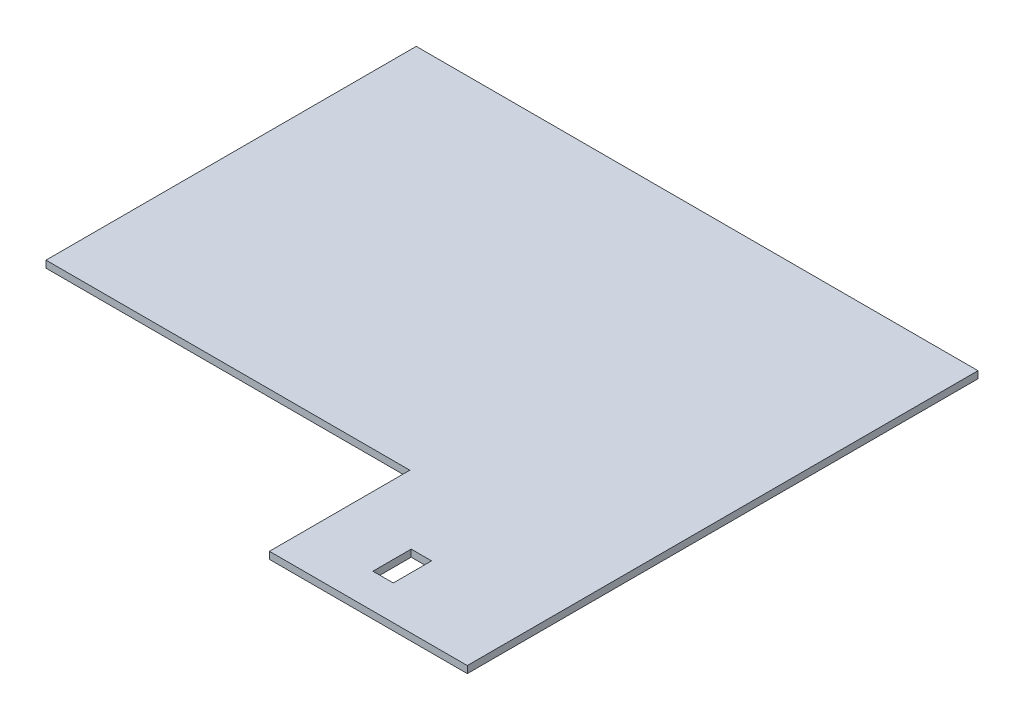
SolidWorks part; units mm, degrees
ref_plane "Alzado" through (0, 0, 0) normal (0, 0, 1) x (1, 0, 0)
ref_plane "Planta" through (0, 0, 0) normal (0, 1, 0) x (1, 0, 0)
ref_plane "Vista lateral" through (0, 0, 0) normal (1, 0, 0) x (0, 0, -1)
sketch "Croquis1" plane through (0, 0, 0) normal (0, 1, 0) x (-1, 0, 0)
  line L19 (-143.5867, 402.2958) -> (-228.5867, 402.2958)
  line L21 (-143.5867, 345.2958) -> (-143.5867, 375.2958)
  line L22 (-228.5867, 2.2958) -> (-228.5867, 402.2958)
  line L24 (211.4133, 2.2958) -> (211.4133, 292.2958)
  line L26 (-228.5867, 2.2958) -> (211.4133, 2.2958)
  line L27 (211.4133, 292.2958) -> (-73.5867, 292.2958)
  line L28 (-143.5867, 402.2958) -> (-73.5867, 402.2958)
  line L29 (-143.5867, 375.2958) -> (-143.5867, 345.2958)
  line L31 (-73.5867, 402.2958) -> (-73.5867, 292.2958)
  line L32 (-143.5867, 375.2958) -> (-127.6253, 375.2958)
  line L33 (-127.6253, 375.2958) -> (-127.6253, 345.2958)
  line L34 (-127.6253, 345.2958) -> (-143.5867, 345.2958)
  line L35 (-143.5867, 375.2958) -> (-143.5867, 345.2958)
  dimension "D1" = 400
  dimension "D2" = 440
  dimension "D3" = 85
  dimension "D4" = 290
  dimension "D5" = 70
  dimension "D7" = 30
  dimension "D8" = 27
extrude "Saliente-Extruir1" add sketch "Croquis1" along normal blind 5.5 contours L31 L28 L19 L22 L26 L24 L27 L33 L34 L21 L32 region at (25.0172, 0, 170.2408)
